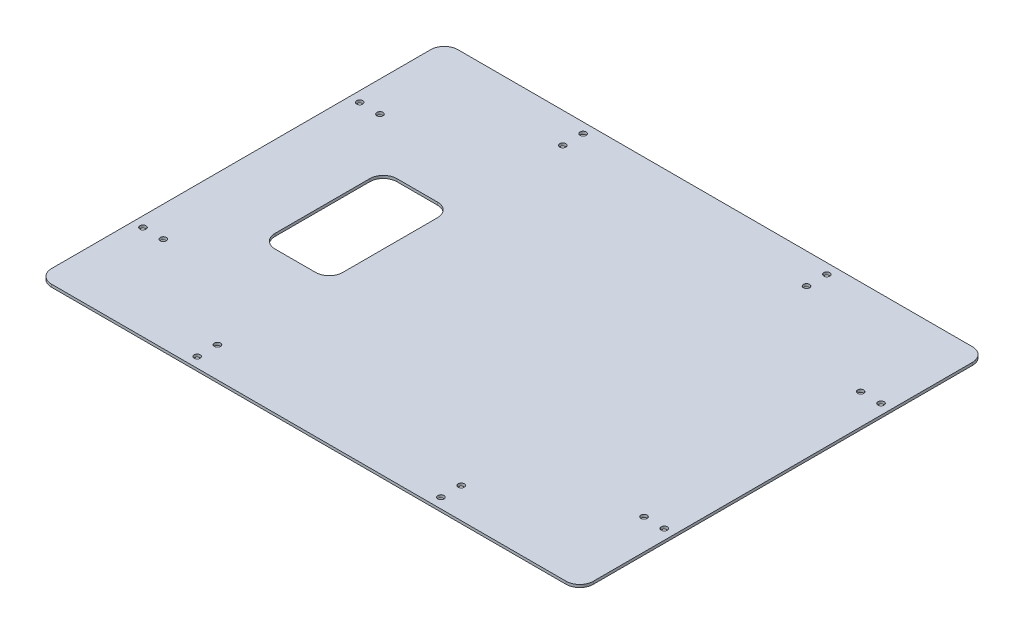
SolidWorks part; units mm, degrees
material "1060 Alloy"
ref_plane "Front Plane" through (0, 0, 0) normal (0, 0, 1) x (1, 0, 0)
ref_plane "Top Plane" through (0, 0, 0) normal (0, 1, 0) x (1, 0, 0)
ref_plane "Right Plane" through (0, 0, 0) normal (1, 0, 0) x (0, 0, -1)
sketch "Sketch5" plane through (0, 0, 0) normal (0, 1, 0) x (1, 0, 0)
  line L1 (0, 0) -> (400, 0)
  line L2 (0, 0) -> (0, 300)
  line L3 (0, 300) -> (400, 300)
  line L4 (400, 0) -> (400, 300)
  dimension "D1" = 400
  dimension "D2" = 300
extrude "Boss-Extrude1" add sketch "Sketch5" along normal blind 2 contours L2 L3 L4 L1
fillet "Fillet1" radius 10 4 edges at (0, 1, -300) (400, 1, -300) (400, 1, 0) (0, 1, 0)
sketch "Sketch6" plane through (0, 2, 0) normal (0, 1, 0) x (1, 0, 0)
  line L1 (70, 195) -> (100, 195)
  line L2 (60, 185) -> (60, 115)
  line L3 (70, 105) -> (100, 105)
  line L4 (110, 185) -> (110, 115)
  line L5 (0, 10) -> (0, 290) construction
  line L6 (85, 195) -> (85, 300) construction
  line L7 (10, 300) -> (390, 300) construction
  line L8 (85, 105) -> (85, 0) construction
  line L9 (10, 0) -> (390, 0) construction
  arc A0 (60, 115) -> (70, 105) centre (70, 115) ccw
  arc A1 (100, 105) -> (110, 115) centre (100, 115) ccw
  arc A2 (100, 195) -> (110, 185) centre (100, 185) cw
  arc A3 (70, 195) -> (60, 185) centre (70, 185) ccw
  dimension "D1" = 10
  dimension "D2" = 50
  dimension "D3" = 90
  dimension "D5" = 60
extrude "Cut-Extrude1" cut sketch "Sketch6" against normal through all
sketch "Sketch7" plane through (0, 2, 0) normal (0, 1, 0) x (1, 0, 0)
  line L0 (10, 0) -> (390, 0) construction
  line L1 (0, 10) -> (0, 290) construction
  line L2 (110, 22.5) -> (110, 7.5) construction
  line L3 (7.5, 70) -> (22.5, 70) construction
  line L4 (200, 300) -> (200, 0) construction
  line L5 (10, 300) -> (390, 300) construction
  line L6 (0, 150) -> (400, 150) construction
  line L7 (400, 10) -> (400, 290) construction
  point P0 (110, 7.5)
  point P1 (110, 22.5)
  point P2 (7.5, 70)
  point P3 (22.5, 70)
  point P20 (290, 7.5)
  point P21 (290, 22.5)
  point P22 (377.5, 70)
  point P23 (392.5, 70)
  point P24 (392.5, 230)
  point P25 (377.5, 230)
  point P26 (290, 292.5)
  point P27 (290, 277.5)
  point P28 (110, 292.5)
  point P29 (110, 277.5)
  point P30 (22.5, 230)
  point P31 (7.5, 230)
  dimension "D1" = 7.5
  dimension "D2" = 15
  dimension "D3" = 7.5
  dimension "D4" = 15
  dimension "D5" = 110
  dimension "D6" = 70
hole_wizard "M4 Clearance Hole1" positions "Sketch7" profile "Sketch8" hole size "M4" standard "ANSI Metric" end condition through all
sketch "Sketch8" plane through (110, 2, -7.5) normal (1, 0, 0) x (0, 0, 1)
  line L0 (0, 0) -> (0, 2)
  line L1 (0, 2) -> (2.25, 2)
  line L2 (2.25, 2) -> (2.25, 0)
  line L5 (2.25, 0) -> (0, 0)
  line L11 (0, -6.35) -> (0, 107.95) construction
  dimension "Thru Hole Dia." = 4.5
  dimension "Thru Hole Depth" = 2
